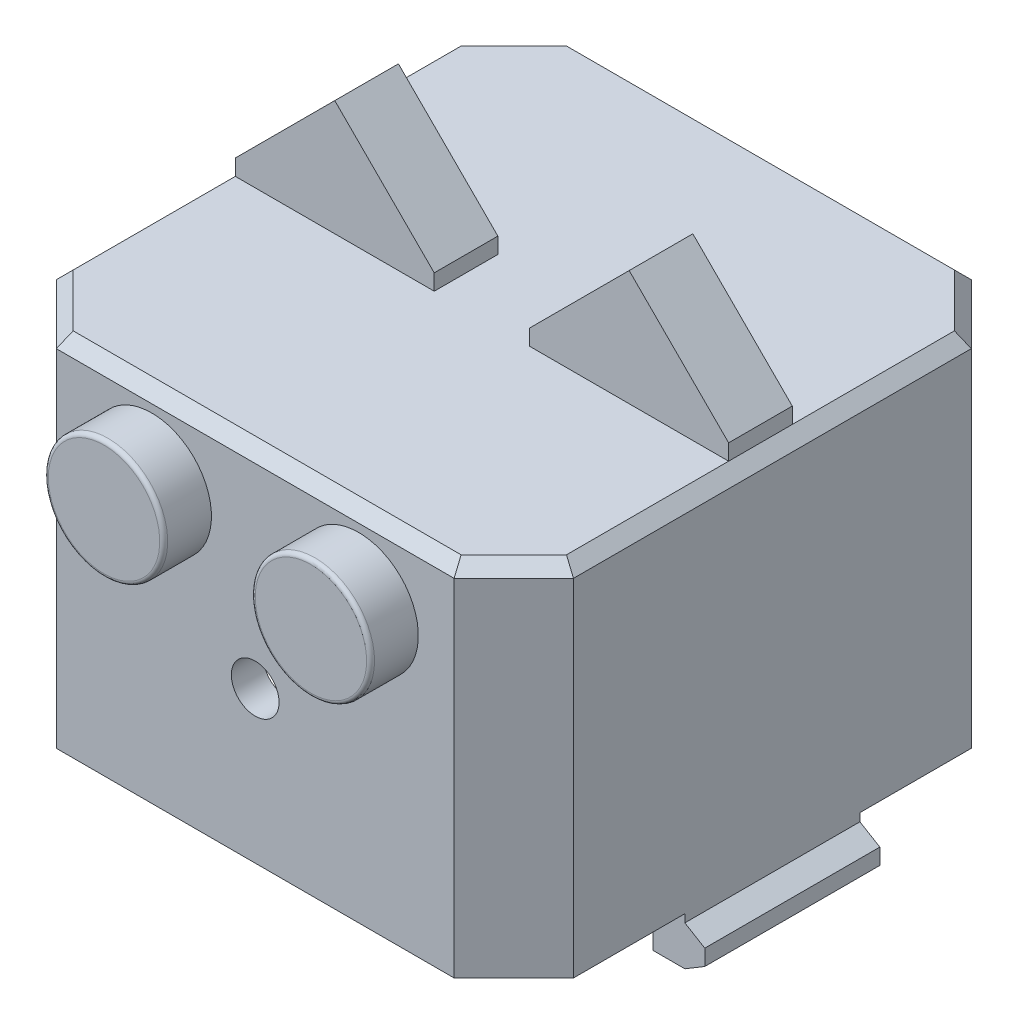
SolidWorks part; units mm, degrees
ref_plane "Alzado" through (0, 0, 0) normal (0, 0, 1) x (1, 0, 0)
ref_plane "Planta" through (0, 0, 0) normal (0, 1, 0) x (1, 0, 0)
ref_plane "Vista lateral" through (0, 0, 0) normal (1, 0, 0) x (0, 0, -1)
sketch "Croquis1" plane through (0, 0, 0) normal (0, 1, 0) x (1, 0, 0)
  line L1 (-25, -32.5) -> (25, -32.5)
  line L3 (-25, 32.5) -> (25, 32.5)
  line L5 (-25, -32.5) -> (25, 32.5) construction
  line L6 (-25, 32.5) -> (25, -32.5) construction
  line L10 (32.5, 25) -> (32.5, -25)
  line L11 (25, -32.5) -> (32.5, -25)
  line L12 (32.5, 25) -> (25, 32.5)
  line L13 (-32.5, 25) -> (-32.5, -25)
  line L14 (-32.5, -25) -> (-25, -32.5)
  line L15 (-32.5, 25) -> (-25, 32.5)
  point P0 (0, 0)
  point P10 (0, 32.5)
  dimension "D1" = 65
  dimension "D2" = 65
  dimension "D3" = 50
  dimension "D4" = 50
  dimension "D5" = 25
  dimension "D6" = 25
extrude "Saliente-Extruir1" add sketch "Croquis1" along normal blind 45
shell "Vaciado2" thickness 4 removed face at (0, 0, 0)
chamfer "Chaflán3" distance 1.5 angle 45 8 edges at (0, 45, -32.5) (32.5, 45, 0) (0, 45, 32.5) (-32.5, 45, 0) (-28.75, 45, 28.75) (28.75, 45, 28.75) (28.75, 45, -28.75) (-28.75, 45, -28.75)
sketch "Croquis2" plane through (0, 0, 32.5) normal (0, 0, 1) x (1, 0, 0)
  line L0 (0, 0) -> (0, 6.916) construction
  circle A0 centre (13, 35) radius 7.5
  circle A1 centre (-13, 35) radius 7.5
  dimension "D1" = 15
  dimension "D2" = 13
  dimension "D3" = 35
extrude "Saliente-Extruir2" add sketch "Croquis2" along normal blind 6
sketch "Croquis4" plane through (0, 0, 28.5) normal (0, 0, -1) x (-1, 0, 0)
  line L0 (0, 0) -> (0, 4.7403) construction
  line L1 (0, 0) -> (0, 6.916) construction
  circle A0 centre (-13, 35) radius 5
  circle A1 centre (13, 35) radius 5
  dimension "D1" = 10
extrude "Cortar-Extruir2" cut sketch "Croquis4" against normal blind 5.5
fillet "Redondeo1" radius 0.5 2 edges at (-20.5, 35, 38.5) (20.5, 35, 38.5)
sketch "Croquis5" plane through (0, 0, 32.5) normal (0, 0, 1) x (1, 0, 0)
  circle A0 centre (0, 19) radius 3
  dimension "D2" = 6
  dimension "D1" = 19
extrude "Cortar-Extruir3" cut sketch "Croquis5" against normal blind 10
sketch "Croquis13" plane through (0, 0, 34) normal (0, 0, -1) x (-1, 0, 0)
  circle A0 centre (-13, 35) radius 2.6
  circle A1 centre (13, 35) radius 2.6
  circle A2 centre (13, 35) radius 5
  circle A3 centre (-13, 35) radius 5
  dimension "D1" = 5.2
  dimension "D2" = 5.2
extrude "Saliente-Extruir8" add sketch "Croquis13" along normal blind 5.5
sketch "Croquis7" plane through (0, 0, 28.5) normal (0, 0, -1) x (-1, 0, 0)
  line L0 (23.3431, 0) -> (-23.3431, 0) construction
  line L1 (-13.58, 8.5) -> (-9.58, 8.5)
  line L2 (-13.58, 8.5) -> (-13.58, 12.5)
  line L3 (-13.58, 12.5) -> (-9.58, 12.5)
  line L4 (-9.58, 8.5) -> (-9.58, 12.5)
  line L5 (-13.58, 8.5) -> (-9.58, 12.5) construction
  line L6 (-13.58, 12.5) -> (-9.58, 8.5) construction
  line L8 (-13.58, 26) -> (-9.58, 26)
  line L9 (-13.58, 26) -> (-13.58, 30)
  line L10 (-13.58, 30) -> (-9.58, 30)
  line L11 (-9.58, 26) -> (-9.58, 30)
  line L12 (-13.58, 26) -> (-9.58, 30) construction
  line L13 (-13.58, 30) -> (-9.58, 26) construction
  line L14 (13.43, 12.5) -> (9.43, 8.5) construction
  line L15 (13.43, 8.5) -> (9.43, 12.5) construction
  line L16 (9.43, 8.5) -> (9.43, 12.5)
  line L17 (13.43, 12.5) -> (9.43, 12.5)
  line L18 (13.43, 8.5) -> (13.43, 12.5)
  line L19 (13.43, 8.5) -> (9.43, 8.5)
  line L20 (13.43, 30) -> (9.43, 26) construction
  line L21 (13.43, 26) -> (9.43, 30) construction
  line L22 (9.43, 26) -> (9.43, 30)
  line L23 (13.43, 30) -> (9.43, 30)
  line L24 (13.43, 26) -> (13.43, 30)
  line L25 (13.43, 26) -> (9.43, 26)
  point P0 (-11.58, 10.5)
  point P8 (-11.58, 28)
  point P13 (0, 0)
  point P15 (11.43, 10.5)
  point P16 (11.43, 28)
  point P20 (11.43, 10.5)
  point P25 (11.43, 28)
  point P26 (-11.58, 28)
  point P27 (11.43, 28)
  point P28 (11.43, 10.5)
  point P29 (-11.58, 10.5)
  dimension "D1" = 10.5
  dimension "D2" = 4
  dimension "D3" = 4
  dimension "D4" = 11.58
  dimension "D5" = 4
  dimension "D6" = 4
  dimension "D7" = 28
  dimension "D8" = 23.01
  dimension "D9" = 23.01
  dimension "D10" = 4
  dimension "D11" = 4
  dimension "D12" = 4
  dimension "D13" = 4
  dimension "D14" = 10.5
  dimension "D15" = 28
extrude "Saliente-Extruir3" add sketch "Croquis7" along normal blind 1
sketch "Croquis8" plane through (0, 0, 27.5) normal (0, 0, -1) x (-1, 0, 0)
  line L0 (0, 0) -> (0, 4.8013) construction
  line L1 (23.3431, 0) -> (-23.3431, 0) construction
  circle A0 centre (-11.505, 10.4893) radius 2
  circle A1 centre (-11.505, 27.9763) radius 2
  circle A2 centre (11.505, 10.4893) radius 2
  circle A3 centre (11.505, 27.9763) radius 2
  dimension "D1" = 4
  dimension "D2" = 4
  dimension "D3" = 23.01
  dimension "D4" = 23.01
extrude "Saliente-Extruir4" add sketch "Croquis8" along normal blind 1
sketch "Croquis9" plane through (0, 0, 26.5) normal (0, 0, -1) x (-1, 0, 0)
  circle A0 centre (-11.505, 27.9763) radius 1.6
  circle A1 centre (-11.505, 10.4893) radius 1.6
  circle A2 centre (11.505, 10.4893) radius 1.6
  circle A3 centre (11.505, 27.9763) radius 1.6
  dimension "D1" = 3.2
  dimension "D2" = 3.2
  dimension "D3" = 3.2
  dimension "D4" = 3.2
extrude "Cortar-Extruir5" cut sketch "Croquis9" against normal blind 2
sketch "Croquis10" plane through (0, 45, 0) normal (0, 1, 0) x (1, 0, 0)
  line L0 (-31, 24.3787) -> (-31, -24.3787) construction
  line L1 (-31, -4) -> (-6, -4)
  line L2 (-31, -4) -> (-31, 4)
  line L3 (-31, 4) -> (-6, 4)
  line L4 (-6, -4) -> (-6, 4)
  line L5 (-31, -4) -> (-6, 4) construction
  line L6 (-31, 4) -> (-6, -4) construction
  line L7 (0, 0) -> (0, 7.307) construction
  line L8 (31, 4) -> (6, -4) construction
  line L9 (31, -4) -> (6, 4) construction
  line L10 (6, -4) -> (6, 4)
  line L11 (31, 4) -> (6, 4)
  line L12 (31, -4) -> (31, 4)
  line L13 (31, -4) -> (6, -4)
  point P0 (-18.5, 0)
  point P14 (18.5, 0)
  dimension "D1" = 25
  dimension "D2" = 8
extrude "Saliente-Extruir5" add sketch "Croquis10" along normal blind 2
sketch "Croquis11" plane through (0, 0, 4) normal (0, 0, 1) x (1, 0, 0)
  line L0 (-31, 47) -> (-6, 47)
  line L1 (-6, 47) -> (-18.5, 59.5)
  line L2 (-31, 47) -> (-18.5, 59.5)
  line L3 (0, 45) -> (0, 52) construction
  line L4 (-24.3787, 45) -> (24.3787, 45) construction
  line L5 (31, 47) -> (18.5, 59.5)
  line L6 (6, 47) -> (18.5, 59.5)
  line L7 (31, 47) -> (6, 47)
extrude "Saliente-Extruir6" add sketch "Croquis11" against normal blind 8
sketch "Croquis12" plane through (0, 41, 0) normal (0, -1, 0) x (1, 0, 0)
  line L0 (0, 0) -> (-5.199, 0) construction
  line L1 (-21.9, -8.93) -> (21.9, -8.93) construction
  line L2 (-21.9, -8.93) -> (-21.9, 8.93) construction
  line L3 (-21.9, 8.93) -> (21.9, 8.93) construction
  line L4 (21.9, -8.93) -> (21.9, 8.93) construction
  line L5 (-21.9, -8.93) -> (21.9, 8.93) construction
  line L6 (-21.9, 8.93) -> (21.9, -8.93) construction
  line L7 (0, 0) -> (0, 4.1573) construction
  circle A0 centre (-20.65, 7.68) radius 0.8
  circle A1 centre (-20.65, 7.68) radius 1.15
  circle A2 centre (-20.65, -7.68) radius 1.15
  circle A3 centre (-20.65, -7.68) radius 0.8
  circle A4 centre (20.65, 7.68) radius 1.15
  circle A5 centre (20.65, 7.68) radius 0.8
  circle A6 centre (20.65, -7.68) radius 1.15
  circle A7 centre (20.65, -7.68) radius 0.8
  point P0 (0, 0)
  dimension "D6" = 1.6
  dimension "D4" = 2.3
  dimension "D1" = 43.8
  dimension "D2" = 17.86
  dimension "D3" = 1.25
  dimension "D7" = 1.25
extrude "Saliente-Extruir7" add sketch "Croquis12" along normal blind 6
sketch "Croquis14" plane through (0, 41, 0) normal (0, -1, 0) x (1, 0, 0)
  line L1 (-22.15, 6.43) -> (-19.15, 6.43)
  line L2 (-22.15, 6.43) -> (-22.15, 8.93)
  line L3 (-22.15, 8.93) -> (-19.15, 8.93)
  line L4 (-19.15, 6.43) -> (-19.15, 8.93)
  line L5 (-22.15, 6.43) -> (-19.15, 8.93) construction
  line L6 (-22.15, 8.93) -> (-19.15, 6.43) construction
  line L7 (-22.15, -8.93) -> (-19.15, -8.93)
  line L8 (-22.15, -8.93) -> (-22.15, -6.43)
  line L9 (-22.15, -6.43) -> (-19.15, -6.43)
  line L10 (-19.15, -8.93) -> (-19.15, -6.43)
  line L11 (-22.15, -8.93) -> (-19.15, -6.43) construction
  line L12 (-22.15, -6.43) -> (-19.15, -8.93) construction
  line L13 (19.15, 6.43) -> (22.15, 6.43)
  line L14 (19.15, 6.43) -> (19.15, 8.93)
  line L15 (19.15, 8.93) -> (22.15, 8.93)
  line L16 (22.15, 6.43) -> (22.15, 8.93)
  line L17 (19.15, 6.43) -> (22.15, 8.93) construction
  line L18 (19.15, 8.93) -> (22.15, 6.43) construction
  line L19 (19.15, -8.93) -> (22.15, -8.93)
  line L20 (19.15, -8.93) -> (19.15, -6.43)
  line L21 (19.15, -6.43) -> (22.15, -6.43)
  line L22 (22.15, -8.93) -> (22.15, -6.43)
  line L23 (19.15, -8.93) -> (22.15, -6.43) construction
  line L24 (19.15, -6.43) -> (22.15, -8.93) construction
  point P0 (-20.65, 7.68)
  point P6 (-20.65, -7.68)
  point P12 (20.65, 7.68)
  point P18 (20.65, -7.68)
  dimension "D1" = 3
  dimension "D2" = 2.5
  dimension "D3" = 3
  dimension "D4" = 2.5
  dimension "D5" = 3
  dimension "D6" = 2.5
  dimension "D7" = 3
  dimension "D8" = 2.5
extrude "Saliente-Extruir9" add sketch "Croquis14" along normal blind 5
sketch "Croquis15" plane through (-32.5, 0, 0) normal (-1, 0, 0) x (0, 0, 1)
  line L1 (-6, 40.5) -> (6, 40.5)
  line L2 (-6, 40.5) -> (-6, 32.5)
  line L3 (-6, 32.5) -> (6, 32.5)
  line L4 (6, 40.5) -> (6, 32.5)
  dimension "D1" = 8
  dimension "D2" = 12
  dimension "D3" = 3
  dimension "D4" = 19
extrude "Cortar-Extruir6" cut sketch "Croquis15" against normal blind 2
sketch "Croquis16" plane through (0, 0, -28.5) normal (0, 0, 1) x (1, 0, 0)
  line L2 (18.95, 6.05) -> (6.55, 6.05)
  line L3 (18.95, 6.05) -> (18.95, 18.45)
  line L4 (18.95, 18.45) -> (6.55, 18.45)
  line L5 (6.55, 6.05) -> (6.55, 18.45)
  line L6 (5.5, 5) -> (20, 5)
  line L7 (5.5, 5) -> (5.5, 19.5)
  line L8 (5.5, 19.5) -> (20, 19.5)
  line L9 (20, 5) -> (20, 19.5)
  line L10 (5.5, 5) -> (20, 19.5) construction
  line L11 (5.5, 19.5) -> (20, 5) construction
  line L12 (18.95, 6.05) -> (6.55, 18.45) construction
  line L13 (18.95, 18.45) -> (6.55, 6.05) construction
  point P0 (12.75, 12.25)
  point P4 (12.75, 12.25)
  dimension "D1" = 12.4
  dimension "D2" = 12.4
  dimension "D3" = 5
  dimension "D4" = 5
  dimension "D5" = 14.5
  dimension "D6" = 14.5
extrude "Saliente-Extruir10" add sketch "Croquis16" along normal blind 3
sketch "Croquis17" plane through (0, 0, -28.5) normal (0, 0, 1) x (1, 0, 0)
  circle A0 centre (12.75, 12.25) radius 5.5
  point P2 (0, 0)
  point P4 (12.75, 12.25)
  dimension "D1" = 11
extrude "Cortar-Extruir7" cut sketch "Croquis17" against normal through all
sketch "Croquis18" plane through (0, 0, 0) normal (0, -1, 0) x (1, 0, 0)
  line L1 (-32.5, 11) -> (-28.5, 11)
  line L2 (-32.5, 11) -> (-32.5, -11)
  line L3 (-32.5, -11) -> (-28.5, -11)
  line L4 (-28.5, 11) -> (-28.5, -11)
  line L5 (-32.5, -25) -> (-32.5, 25) construction
  line L6 (0, 0) -> (0, 8.739) construction
  line L7 (28.5, 11) -> (28.5, -11)
  line L8 (32.5, -11) -> (28.5, -11)
  line L9 (32.5, 11) -> (32.5, -11)
  line L10 (32.5, 11) -> (28.5, 11)
  point P4 (-28.5, 0)
  dimension "D1" = 4
  dimension "D2" = 22
extrude "Saliente-Extruir11" add sketch "Croquis18" along normal blind 6
sketch "Croquis19" plane through (0, 0, 11) normal (0, 0, 1) x (1, 0, 0)
  line L0 (-32.5, -3.5) -> (-35, -3.5) construction
  line L1 (-35, -2.5) -> (-35, -4.5)
  line L2 (-35, -2.5) -> (-32.5, -1)
  line L3 (-32.5, -6) -> (-32.5, 0)
  line L4 (-32.5, -6) -> (-32.5, -1)
  line L5 (-32.5, -6) -> (-35, -4.5)
  line L6 (0, 0) -> (0, 6.3616) construction
  line L7 (-25, 0) -> (25, 0) construction
  line L8 (32.5, -3.5) -> (35, -3.5) construction
  line L9 (32.5, -6) -> (35, -4.5)
  line L10 (32.5, -6) -> (32.5, -1)
  line L11 (32.5, -6) -> (32.5, 0)
  line L12 (35, -2.5) -> (32.5, -1)
  line L13 (35, -2.5) -> (35, -4.5)
  point P18 (-35, -3.5)
  line M6 (-32.5, 0) -> (-32.5, -6)
  dimension "D1" = 2
extrude "Saliente-Extruir13" add sketch "Croquis19" against normal blind 22 contours L5 L2 L1 M6 | L13 L12 L10 L9 region at (-33.5714, -3.5, 11) region at (33.5714, -3.5, 11)
